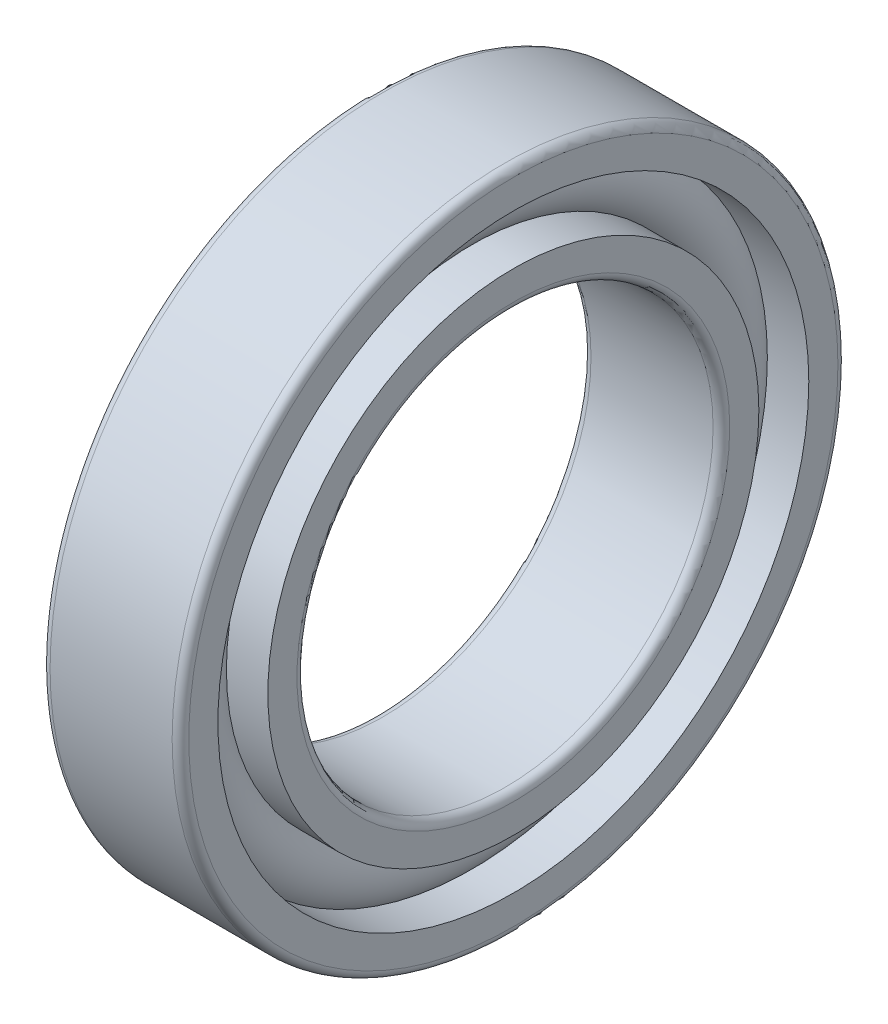
SolidWorks part; units mm, degrees
ref_plane "Plane1" through (0, 0, 0) normal (0, 0, 1) x (1, 0, 0)
ref_plane "Plane2" through (0, 0, 0) normal (0, 1, 0) x (1, 0, 0)
ref_plane "Plane3" through (0, 0, 0) normal (1, 0, 0) x (0, 0, -1)
sketch "Clipboard" plane through (0, 0, 0) normal (0, 0, 1) x (1, 0, 0)
  line L0 (-10, 0) -> (10, 0) construction
  line L1 (0, 0) -> (22.3471, -0.7804)
  line L2 (0, 0) -> (9.7441, 0.3403)
  line L3 (0, 0) -> (22.3471, -0.7804)
  line L4 (0, 0) -> (-22.3573, -0.3902)
  dimension "BallCLRad" = 9.75
sketch "CagSpiSke" plane through (0, 0, 0) normal (0, 0, 1) x (1, 0, 0)
  line L0 (0.135, 9.525) -> (0.135, 9.975)
  line L1 (0.135, 9.975) -> (-0.135, 9.975)
  line L2 (-0.135, 9.975) -> (-0.135, 9.525)
  line L3 (-0.135, 9.525) -> (0.135, 9.525)
  line L4 (-20.6375, 0) -> (20.6375, 0) construction
  line L5 (0, 0) -> (0, 23.7692) construction
  dimension "OD" = 19.95
  dimension "ID" = 19.05
revolve "CageSpine" add sketch "CagSpiSke" angle 0.001 about L4 reverse direction yes
ref_axis "Axis1" through (-50, 0, 0) along (1, 0, 0)
sketch "CagBalSke" plane through (0, 0, 0) normal (0, 0, 1) x (1, 0, 0)
  line L0 (-1.485, 9.75) -> (1.485, 9.75)
  line L1 (-1.905, 9.75) -> (1.905, 9.75) construction
  line L2 (-10, 0) -> (10, 0) construction
  line L3 (0, 0) -> (0, 24) construction
  arc A0 (1.485, 9.75) -> (-1.485, 9.75) centre (0, 9.75) cw
  dimension "BallCLRad" = 9.75
revolve "CageBall" [suppressed] add sketch "CagBalSke" angle 360 about L1 reverse direction yes
pattern_circular "CageBalls" [suppressed] count 2 every 180 about axis through (-50, 0, 0) along (1, 0, 0)
sketch "CagTrmODSke" plane through (0, 0, 0) normal (0, 0, 1) x (1, 0, 0)
  line L0 (1.486, 9.975) -> (1.486, 11.236)
  line L1 (1.486, 11.236) -> (-1.486, 11.236)
  line L2 (-1.486, 11.236) -> (-1.486, 9.975)
  line L3 (-1.486, 9.975) -> (1.486, 9.975)
  line L4 (-20.6375, 0) -> (20.6375, 0) construction
  line L5 (0, 0) -> (0, 25) construction
  dimension "Width" = 2.972
  dimension "ID" = 19.95
  dimension "OD" = 22.472
revolve "CageTrimOD" [suppressed] cut sketch "CagTrmODSke" angle 360 about L4 reverse direction yes
sketch "CagTrmIDSke" plane through (0, 0, 0) normal (0, 0, 1) x (1, 0, 0)
  line L0 (1.486, 8.266) -> (1.486, 9.525)
  line L1 (1.486, 9.525) -> (-1.486, 9.525)
  line L2 (-1.486, 9.525) -> (-1.486, 8.266)
  line L3 (-1.486, 8.266) -> (1.486, 8.266)
  line L4 (-20.6375, 0) -> (20.6375, 0) construction
  line L5 (0, 0) -> (0, 25) construction
  dimension "Width" = 2.972
  dimension "ID" = 16.532
  dimension "OD" = 19.05
revolve "CageTrimID" [suppressed] cut sketch "CagTrmIDSke" angle 360 about L4 reverse direction yes
sketch "BalSimSke" plane through (0, 0, 0) normal (0, 0, 1) x (1, 0, 0)
  line L0 (-10, 0) -> (10, 0) construction
  line L1 (-10, 9.75) -> (10, 9.75) construction
  line L2 (0, 0) -> (0, 23) construction
  circle A0 centre (0, 9.75) radius 1.35
  dimension "BallCLRad" = 9.75
  dimension "Ball_diameter" = 2.7
revolve "BallsSimplified" add sketch "BalSimSke" angle 360 about L0
sketch "BalDetSke" plane through (0, 0, 0) normal (0, 0, 1) x (1, 0, 0)
  line L0 (-1.35, 9.75) -> (1.35, 9.75)
  line L1 (-1.905, 9.75) -> (1.905, 9.75) construction
  line L2 (0, 0) -> (0, 25) construction
  arc A0 (1.35, 9.75) -> (-1.35, 9.75) centre (0, 9.75) cw
  dimension "BallCLRad" = 9.75
  dimension "Ball_diameter" = 2.7
revolve "BallDetailed" [suppressed] add sketch "BalDetSke" angle 360 about L1 reverse direction yes
sketch "InnRacSke" plane through (0, 0, 0) normal (0, 0, 1) x (1, 0, 0)
  line L0 (-0.9724, 8.85) -> (-2.5, 8.85)
  line L1 (-2.5, 8.85) -> (-2.5, 7.8)
  line L2 (-2.2, 7.5) -> (2.2, 7.5)
  line L3 (2.5, 7.8) -> (2.5, 8.85)
  line L4 (2.5, 8.85) -> (0.9724, 8.85)
  line L5 (-20.6375, 0) -> (20.6375, 0) construction
  line L6 (0, 0) -> (0, 30) construction
  arc A0 (-2.5, 7.8) -> (-2.2, 7.5) centre (-2.2, 7.8) ccw
  arc A1 (2.2, 7.5) -> (2.5, 7.8) centre (2.2, 7.8) ccw
  arc A2 (0.9724, 8.85) -> (-0.9724, 8.85) centre (0, 9.75) cw
  dimension "BallCLRad" = 9.75
  dimension "Fillet_radius" = 0.3
  dimension "Ball_diameter" = 2.65
  dimension "ID" = 15
  dimension "OD" = 17.7
  dimension "Width" = 5
revolve "InnerRace" add sketch "InnRacSke" angle 360 about L5 reverse direction yes
sketch "OutRacSke" plane through (0, 0, 0) normal (0, 0, 1) x (1, 0, 0)
  line L0 (-0.9724, 10.65) -> (-2.5, 10.65)
  line L1 (-2.5, 10.65) -> (-2.5, 11.7)
  line L2 (-2.2, 12) -> (2.2, 12)
  line L3 (2.5, 11.7) -> (2.5, 10.65)
  line L4 (2.5, 10.65) -> (0.9724, 10.65)
  line L5 (-20.6375, 0) -> (20.6375, 0) construction
  line L6 (0, 0) -> (0, 30) construction
  arc A0 (-2.5, 11.7) -> (-2.2, 12) centre (-2.2, 11.7) cw
  arc A1 (2.2, 12) -> (2.5, 11.7) centre (2.2, 11.7) cw
  arc A2 (0.9724, 10.65) -> (-0.9724, 10.65) centre (0, 9.75) ccw
  dimension "BallCLRad" = 9.75
  dimension "Fillet_radius" = 0.3
  dimension "Ball_diameter" = 2.65
  dimension "Width" = 5
revolve "OuterRace" add sketch "OutRacSke" angle 360 about L5 reverse direction yes
pattern_circular "BallsDetailed" [suppressed] count 2 every 180 about axis through (-50, 0, 0) along (1, 0, 0)
equation "\"BallCLRad@Clipboard\" = ( \"OD@OutRacSke\" + \"ID@InnRacSke\" ) / 4"
equation "\"BallCLRad@BalSimSke\" = \"BallCLRad@Clipboard\""
equation "\"BallCLRad@BalDetSke\" = \"BallCLRad@Clipboard\""
equation "\"BallCLRad@InnRacSke\" = \"BallCLRad@Clipboard\""
equation "\"BallCLRad@OutRacSke\" = \"BallCLRad@Clipboard\""
equation "\"Ball_diameter@InnRacSke\" = \"Ball_diameter@BalDetSke\" - 0.05"
equation "\"Ball_diameter@OutRacSke\" = \"Ball_diameter@BalDetSke\" - 0.05"
equation "\"Ball_diameter@BalSimSke\" = \"Ball_diameter@BalDetSke\""
equation "\"Width@OutRacSke\" = \"Width@InnRacSke\""
equation "\"Fillet_radius@OutRacSke\" = \"Fillet_radius@InnRacSke\""
equation "\"Max_count@Clipboard\" = int( 3.14159265 / atn(( \"Ball_diameter@BalDetSke\" / 2) / sqr( \"BallCLRad@Clipboard\"  *  \"BallCLRad@Clipboard\" - ( \"Ball_diameter@BalDetSke\" / 2) *  ( \"Ball_diameter@BalDetSke\" / 2))))"
equation "\"Max_count@Clipboard\" = ((sgn( \"Max_count@Clipboard\" - \"Count@Clipboard\" )-1)*( \"Max_count@Clipboard\" - \"Count@Clipboard\" ))/-2+ \"Count@Clipboard\""
equation "\"Count@BallsDetailed\" = int( \"Show_count@Clipboard\" ) "
equation "\"Count@BallsDetailed\" = ((sgn( \"Count@BallsDetailed\" - \"Max_count@Clipboard\" )-1)*( \"Count@BallsDetailed\" - \"Max_count@Clipboard\" ))/-2+ \"Max_count@Clipboard\""
equation "\"Count@BallsDetailed\" = ((sgn( \"Count@BallsDetailed\" - \"Min_count@Clipboard\" )+1)*( \"Count@BallsDetailed\" - \"Min_count@Clipboard\"))/2 +\"Min_count@Clipboard\""
equation "\"Angle@BallsDetailed\" = 360.0 / \"Max_count@Clipboard\""
equation "\"BallCLRad@CagBalSke\" = \"BallCLRad@Clipboard\""
equation "\"Count@CageBalls\" = \"Count@BallsDetailed\""
equation "\"Angle@CageBalls\" = \"Angle@BallsDetailed\""
equation "\"Angle@CageSpine\" =  \"Angle@CageBalls\" * ( \"Count@CageBalls\" -1 + int( \"Count@CageBalls\" / \"Max_count@Clipboard\" ) )  + 0.001 -  int( \"Count@CageBalls\" / \"Max_count@Clipboard\" ) * 0.001"
equation "\"Angle@CageSpine\" =  \"Angle@CageSpine\" * int( \"Min_count@Clipboard\" / 2) + int(1 / \"Min_count@Clipboard\")  * 0.001"
equation "\"CageWallOD@CagBalSke\" =  \"Ball_diameter@BalDetSke\" * 1.1"
equation "\"Thickness@CagSpiSke\" =  \"Ball_diameter@BalDetSke\" * 0.1"
equation "\"OD@CagTrmODSke\" = \"BallCLRad@Clipboard\" * 2 + \"CageWallOD@CagBalSke\" + 0.002"
equation "\"ID@CagTrmODSke\" = \"BallCLRad@Clipboard\" * 2 + \"Ball_diameter@BalDetSke\" / 6"
equation "\"OD@CagTrmIDSke\" = \"BallCLRad@Clipboard\" * 2 - \"Ball_diameter@BalDetSke\" / 6"
equation "\"ID@CagTrmIDSke\" = \"BallCLRad@Clipboard\" * 2 - \"CageWallOD@CagBalSke\" + 0.002"
equation "\"OD@CagSpiSke\" = \"ID@CagTrmODSke\""
equation "\"ID@CagSpiSke\" = \"OD@CagTrmIDSke\""
equation "\"Width@CagTrmODSke\" = \"CageWallOD@CagBalSke\" + 0.002"
equation "\"Width@CagTrmIDSke\" = \"CageWallOD@CagBalSke\" + 0.002"
